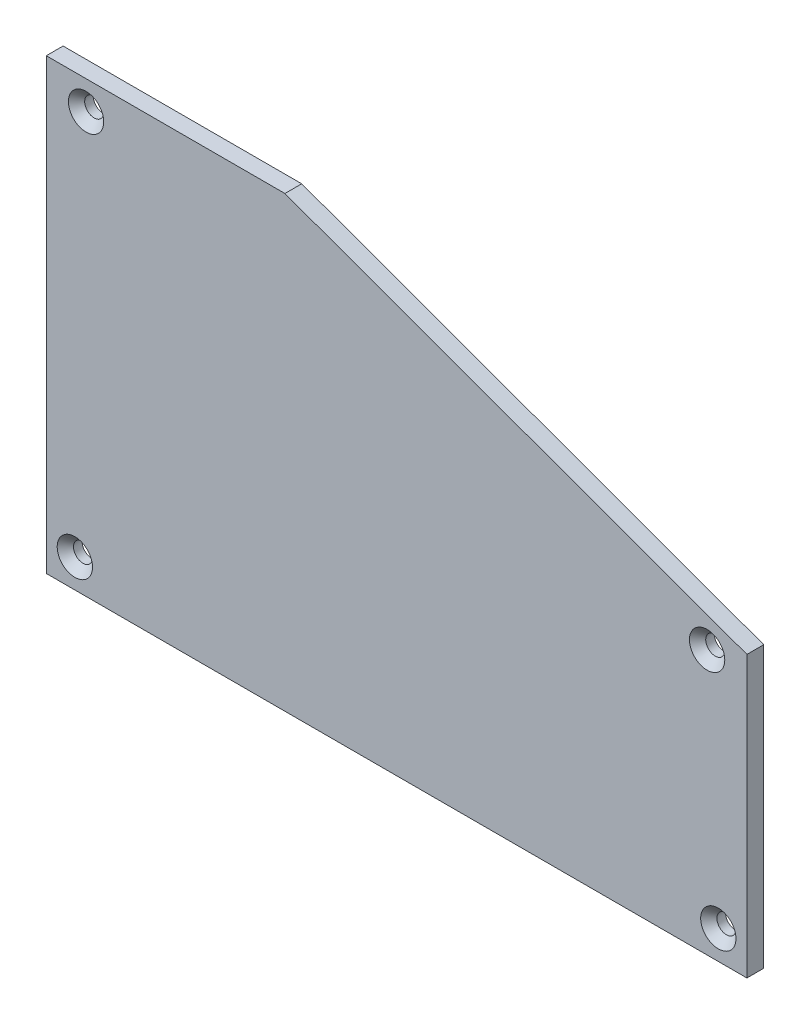
SolidWorks part; units mm, degrees
ref_plane "Спереди" through (0, 0, 0) normal (0, 0, 1) x (1, 0, 0)
ref_plane "Сверху" through (0, 0, 0) normal (0, 1, 0) x (1, 0, 0)
ref_plane "Справа" through (0, 0, 0) normal (1, 0, 0) x (0, 0, -1)
sketch "Эскиз1" plane through (0, 0, 0) normal (0, 0, 1) x (1, 0, 0)
  line L10 (-19.9243, 80) -> (62.5, 50) construction
  line L11 (-62.5, 80) -> (-19.9243, 80) construction
  line L12 (-62.5, 0) -> (-62.5, 80) construction
  line L13 (62.5, 0) -> (-62.5, 0) construction
  line L14 (62.5, 50) -> (62.5, 0) construction
  line L15 (-19.9243, 80) -> (62.5, 50)
  line L16 (-62.5, 80) -> (-19.9243, 80)
  line L17 (-62.5, 0) -> (-62.5, 80)
  line L18 (62.5, 0) -> (-62.5, 0)
  line L19 (62.5, 50) -> (62.5, 0)
extrude "Бобышка-Вытянуть1" add sketch "Эскиз1" along normal blind 3
hole_wizard "Зенковка для винта с потайной головкой M31" positions "Эскиз4" profile "Эскиз5" countersink size "M3" standard "DIN" end condition through all
sketch "Эскиз4" plane through (0, 0, 3) normal (0, 0, 1) x (1, 0, 0)
  point P0 (-55.4, 74.9)
  point P3 (-57.4, 5.1)
  point P7 (55.4, 47.1569)
  point P10 (57.4, 5.1)
sketch "Эскиз5" plane through (-55.4, 74.9, 3) normal (1, 0, 0) x (0, -1, 0)
  line L0 (0, 0) -> (0, 3)
  line L1 (0, 3) -> (1.7, 3)
  line L2 (1.7, 3) -> (1.7, 1.45)
  line L3 (1.7, 1.45) -> (3.15, 0)
  line L5 (3.15, 0) -> (0, 0)
  line L6 (-1.7, 1.45) -> (-3.15, 0) construction
  line L11 (0, -6.35) -> (0, 107.95) construction
  dimension "Диаметр сквозного отверстия" = 3.4
  dimension "Глубина сквозного отверстия" = 3
  dimension "Диаметр передней зенковки" = 6.3
  dimension "Угол передней зенковки" = 90
